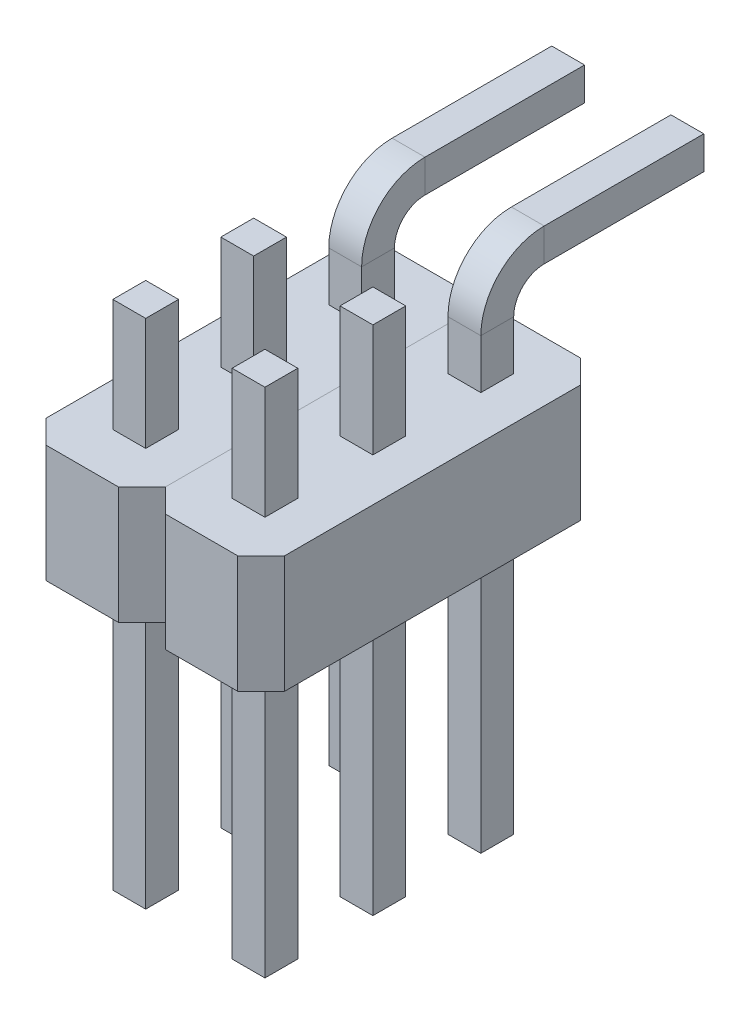
SolidWorks part; units mm, degrees
material "201 Annealed Stainless Steel (SS)"
ref_plane "Front Plane" through (0, 0, 0) normal (0, 0, 1) x (1, 0, 0)
ref_plane "Top Plane" through (0, 0, 0) normal (0, 1, 0) x (1, 0, 0)
ref_plane "Right Plane" through (0, 0, 0) normal (1, 0, 0) x (0, 0, -1)
sketch "Sketch1" plane through (0, 0, 0) normal (0, 1, 0) x (1, 0, 0)
  line L0 (0, 0) -> (2.54, 0)
  line L1 (0, 0) -> (0, -7.3)
  line L2 (0, -7.3) -> (2.54, -7.3)
  line L3 (2.54, 0) -> (2.54, -7.3)
  line L4 (0.92, -1) -> (1.62, -1)
  line L5 (0.92, -1) -> (0.92, -1.7)
  line L6 (0.92, -1.7) -> (1.62, -1.7)
  line L7 (1.62, -1) -> (1.62, -1.7)
  line L8 (0.92, -5.6) -> (1.62, -5.6)
  line L9 (0.92, -5.6) -> (0.92, -6.3)
  line L10 (0.92, -6.3) -> (1.62, -6.3)
  line L11 (1.62, -5.6) -> (1.62, -6.3)
  line L12 (0.92, -3.3) -> (1.62, -3.3)
  line L13 (0.92, -3.3) -> (0.92, -4)
  line L14 (0.92, -4) -> (1.62, -4)
  line L15 (1.62, -3.3) -> (1.62, -4)
  dimension "D1" = 7.3
  dimension "D2" = 2.54
  dimension "D3" = 0.92
  dimension "D4" = 1
  dimension "D5" = 0.7
  dimension "D6" = 1.6
  dimension "D7" = 1.6
ref_plane "Plane1" through (1.25, 0, 0) normal (1, 0, 0) x (0, 0, -1)
sketch "Sketch2" plane through (1.25, 0, 0) normal (1, 0, 0) x (0, 0, -1)
  line L0 (-5.95, 8.15) -> (-5.95, -6)
  line L1 (-3.65, 5.85) -> (-3.65, -6)
  line L2 (-1.35, 3.55) -> (-1.35, -6)
  line L3 (-4.95, 9.15) -> (3.05, 9.15)
  line L4 (0, 0) -> (-7.3, 0) construction
  line L5 (-2.65, 6.85) -> (3.05, 6.85)
  line L6 (-0.35, 4.55) -> (3.05, 4.55)
  arc A0 (-1.35, 3.55) -> (-0.35, 4.55) centre (-0.35, 3.55) cw
  arc A1 (-3.65, 5.85) -> (-2.65, 6.85) centre (-2.65, 5.85) cw
  arc A2 (-5.95, 8.15) -> (-4.95, 9.15) centre (-4.95, 8.15) cw
  point P19 (-5.95, 9.15)
  dimension "D9" = 1
  dimension "D1" = 15.15
  dimension "D2" = 2.3
  dimension "D3" = 2.3
  dimension "D4" = 1.35
  dimension "D5" = 6
  dimension "D6" = 9
  dimension "D7" = 2.3
  dimension "D8" = 2.3
sweep "Sweep3" add profiles "Sketch1" path "Sketch2"
sweep "Sweep4" add profiles "Sketch1<5>" path "Sketch2<6>"
sketch "Sketch1<5>" plane through (0, 0, 0) normal (0, 1, 0) x (1, 0, 0) same geometry as "Sketch1"
sketch "Sketch2<6>" plane through (1.25, 0, 0) normal (1, 0, 0) x (0, 0, -1) same geometry as "Sketch2"
sweep "Sweep5" add profiles "Sketch1<6>" path "Sketch2<7>"
sketch "Sketch1<6>" plane through (0, 0, 0) normal (0, 1, 0) x (1, 0, 0) same geometry as "Sketch1"
sketch "Sketch2<7>" plane through (1.25, 0, 0) normal (1, 0, 0) x (0, 0, -1) same geometry as "Sketch2"
extrude "Boss-Extrude1" add sketch "Sketch1<7>" along normal blind 2.5 separate body contours L3 L0 L1 L2 L4 L7 L6 L5 L8 L11 L10 L9 L12 L15 L14 L13 region at (1.27, 0, 0.0773)
sketch "Sketch1<7>" plane through (0, 0, 0) normal (0, 1, 0) x (1, 0, 0) same geometry as "Sketch1"
chamfer "Chamfer1" distance 0.5 angle 45 4 edges at (0, 1.25, 0) (2.54, 1.25, 0) (0, 1.25, 7.3) (2.54, 1.25, 7.3)
pattern_linear "LPattern1" count 2 spacing 2.54 along (1, 0, 0) of bodies 103 102 101 104
sketch "Sketch3" plane through (0, 4.9, 0) normal (0, 1, 0) x (1, 0, 0)
  line L0 (0, 3.05) -> (5.08, 3.05)
  line L1 (5.08, 3.05) -> (5.08, -7.3)
  line L2 (5.08, -7.3) -> (0, -7.3)
  line L3 (0, -7.3) -> (0, 3.05)
  line L4 (1.62, 3.05) -> (0.92, 3.05) construction
  line L7 (0, -7.3) -> (2.54, -7.3) construction
  line L8 (5.08, -0.5) -> (5.08, -6.8) construction
extrude "Cut-Extrude1" cut sketch "Sketch3" along normal through all contours L3 L0 L1 L2
